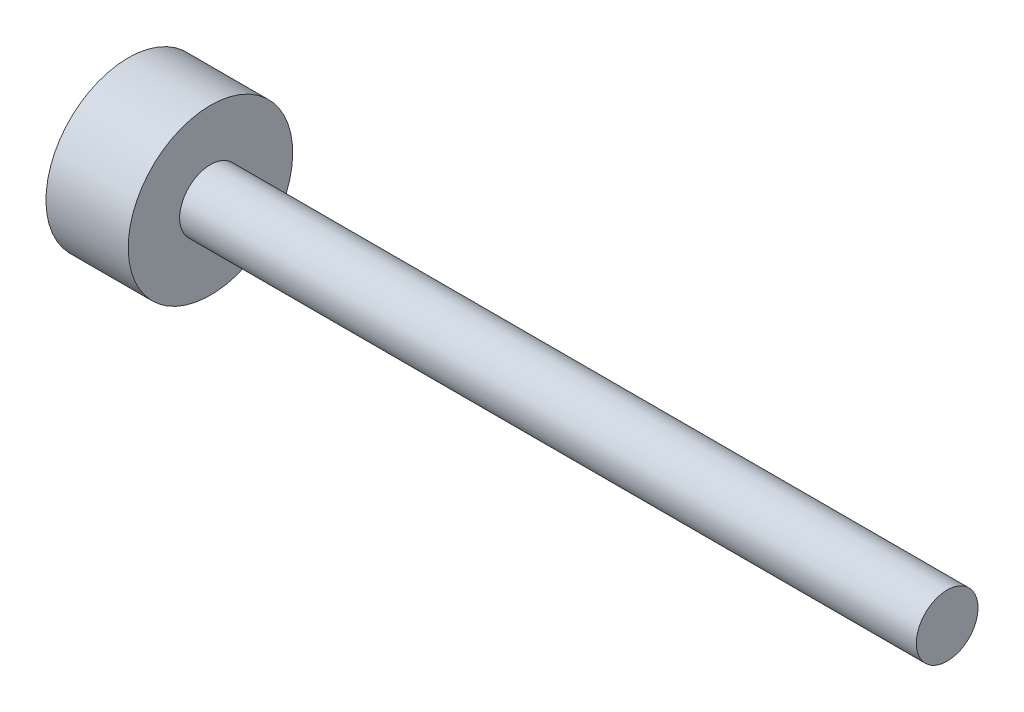
SolidWorks part; units mm, degrees
material "Delrin 2700 NC010, Low Viscosity Acetal Copolymer (SS)"
ref_plane "Front Plane" through (0, 0, 0) normal (0, 0, 1) x (1, 0, 0)
ref_plane "Top Plane" through (0, 0, 0) normal (0, 1, 0) x (1, 0, 0)
ref_plane "Right Plane" through (0, 0, 0) normal (1, 0, 0) x (0, 0, -1)
sketch "Sketch1" plane through (0, 0, 0) normal (0, 0, 1) x (1, 0, 0)
  line L0 (0, 0) -> (-19.914, 0) construction
  line L2 (0, 0) -> (-17.914, 0)
  line L3 (0, 0) -> (0, 0.75)
  line L4 (0, 0.75) -> (-17.914, 0.75)
  line L5 (-17.914, 0) -> (-17.914, 0.75)
  line L6 (-17.914, 0) -> (-19.914, 0)
  line L7 (-17.914, 0) -> (-17.914, 2)
  line L8 (-17.914, 2) -> (-19.914, 2)
  line L9 (-19.914, 0) -> (-19.914, 2)
  dimension "D1" = 2
  dimension "D2" = 17.914
  dimension "D3" = 2
  dimension "D4" = 0.75
revolve "Revolve1" add sketch "Sketch1" angle 360 about L0 region at (-8.957, 0.375, 0) region at (-18.914, 1, 0)
